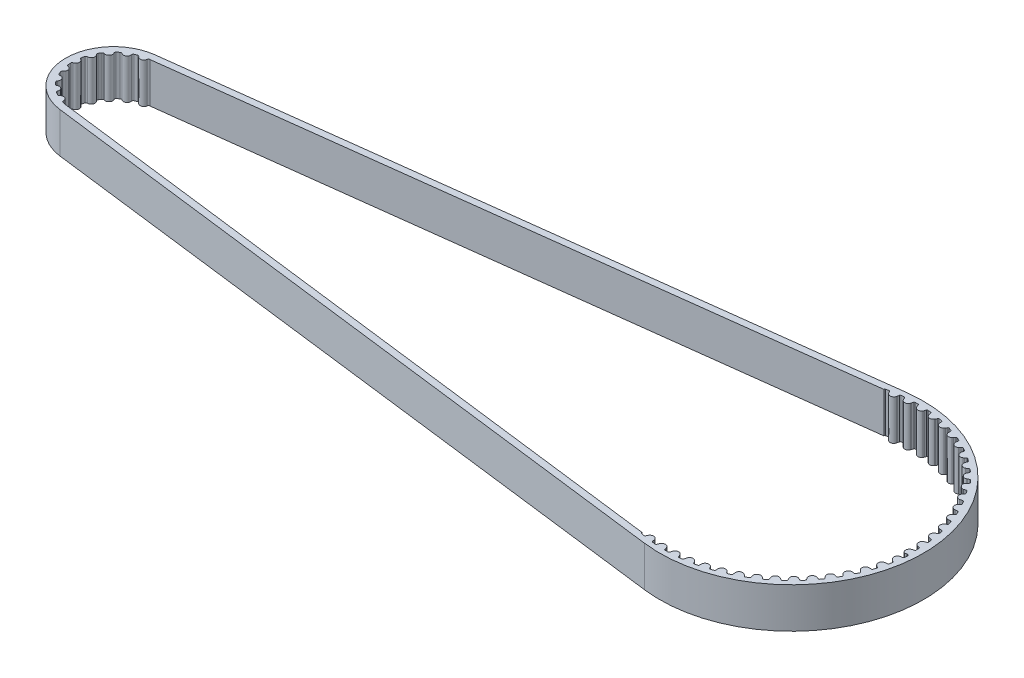
SolidWorks part; units mm, degrees
material "Rubber"
ref_plane "Front Plane" through (0, 0, 0) normal (0, 0, 1) x (1, 0, 0)
ref_plane "Top Plane" through (0, 0, 0) normal (0, 1, 0) x (1, 0, 0)
ref_plane "Right Plane" through (0, 0, 0) normal (1, 0, 0) x (0, 0, -1)
sketch "Sketch1" plane through (0, 0, 0) normal (0, 1, 0) x (1, 0, 0)
  line L0 (0, 0) -> (101, 0)
  line L1 (99.6245, -18.6906) -> (99.7039, -18.4765)
  line L2 (100.8046, -18.5209) -> (100.8665, -18.7407)
  line L3 (101.5857, -18.732) -> (101.6423, -18.5108)
  line L4 (102.7417, -18.4399) -> (102.8262, -18.652)
  line L5 (103.5405, -18.5682) -> (103.5737, -18.3423)
  line L6 (104.6596, -18.1568) -> (104.7659, -18.3589)
  line L7 (105.4675, -18.2009) -> (105.4769, -17.9728)
  line L8 (106.5375, -17.6748) -> (106.6643, -17.8647)
  line L9 (107.3455, -17.6342) -> (107.331, -17.4064)
  line L10 (108.3547, -16.9992) -> (108.5006, -17.1747)
  line L11 (109.1541, -16.8743) -> (109.1158, -16.6492)
  line L12 (110.0913, -16.1373) -> (110.2548, -16.2966)
  line L13 (110.8732, -15.9295) -> (110.8116, -15.7097)
  line L14 (111.7283, -15.0986) -> (111.9075, -15.24)
  line L15 (112.4842, -14.8102) -> (112.4, -14.598)
  line L16 (113.2477, -13.8944) -> (113.4408, -14.0163)
  line L17 (113.9694, -13.5287) -> (113.8635, -13.3264)
  line L18 (114.633, -12.5381) -> (114.8377, -12.6391)
  line L19 (115.3125, -12.0989) -> (115.186, -11.9088)
  line L20 (115.8689, -11.0444) -> (116.0831, -11.1235)
  line L21 (116.4988, -10.5365) -> (116.3531, -10.3608)
  line L22 (116.9419, -9.4296) -> (117.1632, -9.4859)
  line L23 (117.5152, -8.8588) -> (117.352, -8.6992)
  line L24 (117.8402, -7.7116) -> (118.0662, -7.7444)
  line L25 (118.3508, -7.0839) -> (118.1717, -6.9423)
  line L26 (118.5541, -5.9091) -> (118.7822, -5.9181)
  line L27 (118.9962, -5.2315) -> (118.8033, -5.1093)
  line L28 (119.0756, -4.0418) -> (119.3034, -4.0269)
  line L29 (119.4444, -3.3217) -> (119.2398, -3.2204)
  line L30 (119.4169, -2.1154) -> (119.6419, -2.0768)
  line L31 (119.7085, -1.3607) -> (119.4944, -1.2813)
  line L32 (119.3436, -0.3425) -> (119.5634, -0.2806)
  line L33 (119.5547, 0.4386) -> (119.3335, 0.4952)
  line L34 (119.2626, 1.5945) -> (119.4747, 1.6791)
  line L35 (119.3909, 2.3934) -> (119.165, 2.4265)
  line L36 (118.9795, 3.5125) -> (119.1816, 3.6187)
  line L37 (119.0236, 4.3204) -> (118.7955, 4.3297)
  line L38 (118.4975, 5.3903) -> (118.6874, 5.5171)
  line L39 (118.4569, 6.1984) -> (118.2291, 6.1839)
  line L40 (117.8219, 7.2075) -> (117.9975, 7.3535)
  line L41 (117.697, 8.0069) -> (117.472, 7.9687)
  line L42 (116.96, 8.9441) -> (117.1194, 9.1076)
  line L43 (116.7523, 9.7261) -> (116.5324, 9.6645)
  line L44 (115.9213, 10.5811) -> (116.0627, 10.7604)
  line L45 (115.633, 11.3371) -> (115.4208, 11.2529)
  line L46 (114.8944, 12.2477) -> (115.0163, 12.4408)
  line L47 (114.5287, 12.9694) -> (114.3264, 12.8635)
  line L48 (113.5381, 13.633) -> (113.6391, 13.8377)
  line L49 (113.0989, 14.3125) -> (112.9088, 14.186)
  line L50 (112.0444, 14.8689) -> (112.1235, 15.0831)
  line L51 (111.5365, 15.4988) -> (111.3608, 15.3531)
  line L52 (110.4296, 15.9419) -> (110.4859, 16.1632)
  line L53 (109.8588, 16.5152) -> (109.6992, 16.352)
  line L54 (108.7116, 16.8402) -> (108.7444, 17.0662)
  line L55 (108.0839, 17.3508) -> (107.9423, 17.1717)
  line L56 (106.9091, 17.5541) -> (106.9181, 17.7822)
  line L57 (106.2315, 17.9962) -> (106.1093, 17.8033)
  line L58 (105.0418, 18.0756) -> (105.0269, 18.3034)
  line L59 (104.3217, 18.4444) -> (104.2204, 18.2398)
  line L60 (103.1303, 18.399) -> (103.0917, 18.6241)
  line L61 (102.3755, 18.6906) -> (102.2961, 18.4765)
  line L62 (101.1954, 18.5209) -> (101.1335, 18.7407)
  line L63 (100.4143, 18.732) -> (100.3577, 18.5108)
  line L64 (99.2583, 18.4399) -> (99.1738, 18.652)
  line L65 (98.4595, 18.5682) -> (98.4263, 18.3423)
  line L66 (97.3404, 18.1568) -> (97.2341, 18.3589)
  line L67 (96.5325, 18.2009) -> (96.5231, 17.9728)
  line L68 (95.4625, 17.6748) -> (95.3357, 17.8647)
  line L69 (94.6545, 17.6342) -> (94.669, 17.4064)
  line L70 (93.6453, 16.9992) -> (93.4994, 17.1747)
  line L71 (92.8459, 16.8743) -> (92.8842, 16.6492)
  line L72 (91.9087, 16.1373) -> (91.7452, 16.2966)
  line L73 (91.1268, 15.9295) -> (91.1884, 15.7097)
  line L74 (90.2717, 15.0986) -> (90.0925, 15.24)
  line L75 (89.5158, 14.8102) -> (89.6, 14.598)
  line L76 (88.7523, 13.8944) -> (88.5592, 14.0163)
  line L77 (88.0306, 13.5287) -> (88.1365, 13.3264)
  line L78 (87.367, 12.5381) -> (87.1623, 12.6391)
  line L79 (86.6875, 12.0989) -> (86.814, 11.9088)
  line L80 (86.1311, 11.0444) -> (85.9169, 11.1235)
  line L81 (85.5012, 10.5365) -> (85.6469, 10.3608)
  line L82 (85.0581, 9.4296) -> (84.8368, 9.4859)
  line L83 (84.4848, 8.8588) -> (84.648, 8.6992)
  line L84 (84.1598, 7.7116) -> (83.9338, 7.7444)
  line L85 (83.6492, 7.0839) -> (83.8283, 6.9423)
  line L86 (83.4459, 5.9091) -> (83.2178, 5.9181)
  line L87 (83.0038, 5.2315) -> (83.1967, 5.1093)
  line L88 (82.9244, 4.0418) -> (82.6966, 4.0269)
  line L89 (82.5556, 3.3217) -> (82.7602, 3.2204)
  line L90 (82.601, 2.1303) -> (82.3759, 2.0917)
  line L91 (82.3094, 1.3755) -> (82.5235, 1.2961)
  line L92 (82.4791, 0.1954) -> (82.2593, 0.1335)
  line L93 (82.268, -0.5857) -> (82.4892, -0.6423)
  line L94 (82.5601, -1.7417) -> (82.348, -1.8262)
  line L95 (82.4318, -2.5405) -> (82.6577, -2.5737)
  line L96 (82.8432, -3.6596) -> (82.6411, -3.7659)
  line L97 (82.7991, -4.4675) -> (83.0272, -4.4769)
  line L98 (83.3252, -5.5375) -> (83.1353, -5.6643)
  line L99 (83.3658, -6.3455) -> (83.5936, -6.331)
  line L100 (84.0008, -7.3547) -> (83.8253, -7.5006)
  line L101 (84.1257, -8.1541) -> (84.3508, -8.1158)
  line L102 (84.8627, -9.0913) -> (84.7034, -9.2548)
  line L103 (85.0705, -9.8732) -> (85.2903, -9.8116)
  line L104 (85.9014, -10.7283) -> (85.76, -10.9075)
  line L105 (86.1898, -11.4842) -> (86.402, -11.4)
  line L106 (87.1056, -12.2477) -> (86.9837, -12.4408)
  line L107 (87.4713, -12.9694) -> (87.6736, -12.8635)
  line L108 (88.4619, -13.633) -> (88.3609, -13.8377)
  line L109 (88.9011, -14.3125) -> (89.0912, -14.186)
  line L110 (89.9556, -14.8689) -> (89.8765, -15.0831)
  line L111 (90.4635, -15.4988) -> (90.6392, -15.3531)
  line L112 (91.5704, -15.9419) -> (91.5141, -16.1632)
  line L113 (92.1412, -16.5152) -> (92.3008, -16.352)
  line L114 (93.2884, -16.8402) -> (93.2556, -17.0662)
  line L115 (93.9161, -17.3508) -> (94.0577, -17.1717)
  line L116 (95.0909, -17.5541) -> (95.0819, -17.7822)
  line L117 (95.7685, -17.9962) -> (95.8907, -17.8033)
  line L118 (96.9582, -18.0756) -> (96.9731, -18.3034)
  line L119 (97.6783, -18.4444) -> (97.7796, -18.2398)
  line L120 (98.8697, -18.399) -> (98.9083, -18.6241)
  line L121 (-0.8821, -7.0702) -> (98.5701, -19.4775)
  line L122 (-0.8821, 7.0702) -> (98.5701, 19.4775)
  line L123 (98.2274, -18.421) -> (-1.1005, -6.0253)
  line L124 (-0.5636, 6.099) -> (97.864, 18.3626)
  circle A0 centre (0, 0) radius 7.125
  arc A1 (3.5613, -4.8212) -> (2.6742, -5.3656) centre (3.2108, -5.2451) ccw
  arc A2 (2.5625, -5.5912) -> (2.6742, -5.3656) centre (2.4791, -5.4094) ccw
  arc A3 (2.1438, -5.7649) -> (2.5625, -5.5912) centre (0.0074, -0.0246) ccw
  arc A4 (1.9052, -5.6847) -> (2.1438, -5.7649) centre (2.074, -5.5775) ccw
  arc A5 (1.9052, -5.6847) -> (0.8932, -5.9283) centre (1.4408, -5.9795) ccw
  arc A6 (0.7173, -6.1083) -> (0.8932, -5.9283) centre (0.6941, -5.9096) ccw
  arc A7 (0.2653, -6.1441) -> (0.7173, -6.1083) centre (0.0074, -0.0246) ccw
  arc A8 (0.0632, -5.9941) -> (0.2653, -6.1441) centre (0.2569, -5.9443) ccw
  arc A9 (0.0632, -5.9941) -> (-0.9745, -5.9131) centre (-0.4695, -6.131) ccw
  arc A10 (-1.1974, -6.0299) -> (-0.9745, -5.9131) centre (-1.1581, -5.8338) ccw
  arc A11 (-1.6457, -5.8998) -> (-1.1974, -6.0299) centre (0.2848, -0.087) ccw
  arc A12 (-1.7916, -5.6946) -> (-1.6457, -5.8998) centre (-1.592, -5.7071) ccw
  arc A13 (-1.7916, -5.6946) -> (-2.7535, -5.2969) centre (-2.3405, -5.6602) ccw
  arc A14 (-3.0016, -5.3391) -> (-2.7535, -5.2969) centre (-2.9036, -5.1648) ccw
  arc A15 (-3.3883, -5.1024) -> (-3.0016, -5.3391) centre (0, 0) ccw
  arc A16 (-3.4636, -4.8622) -> (-3.3883, -5.1024) centre (-3.2777, -4.9358) ccw
  arc A17 (-3.4636, -4.8622) -> (-4.2555, -4.1868) centre (-3.9751, -4.6599) ccw
  arc A18 (-4.5046, -4.1502) -> (-4.2555, -4.1868) centre (-4.3575, -4.0147) ccw
  arc A19 (-4.7992, -3.8057) -> (-4.5046, -4.1502) centre (0, 0) ccw
  arc A20 (-4.7966, -3.5539) -> (-4.7992, -3.8057) centre (-4.6425, -3.6814) ccw
  arc A21 (-4.7966, -3.5539) -> (-5.341, -2.6668) centre (-5.2205, -3.2034) ccw
  arc A22 (-5.5666, -2.5551) -> (-5.341, -2.6668) centre (-5.3848, -2.4717) ccw
  arc A23 (-5.7403, -2.1364) -> (-5.5666, -2.5551) centre (0, 0) ccw
  arc A24 (-5.6601, -1.8978) -> (-5.7403, -2.1364) centre (-5.5529, -2.0666) ccw
  arc A25 (-5.6601, -1.8978) -> (-5.9037, -0.8858) centre (-5.9549, -1.4334) ccw
  arc A26 (-6.0837, -0.7099) -> (-5.9037, -0.8858) centre (-5.8851, -0.6867) ccw
  arc A27 (-6.1196, -0.2579) -> (-6.0837, -0.7099) centre (0, 0) ccw
  arc A28 (-5.9695, -0.0558) -> (-6.1196, -0.2579) centre (-5.9197, -0.2495) ccw
  arc A29 (-5.9695, -0.0558) -> (-5.8885, 0.9819) centre (-6.1064, 0.4769) ccw
  arc A30 (-6.0053, 1.2048) -> (-5.8885, 0.9819) centre (-5.8092, 1.1655) ccw
  arc A31 (-5.8998, 1.6457) -> (-6.0053, 1.2048) centre (0, 0) ccw
  arc A32 (-5.6946, 1.7916) -> (-5.8998, 1.6457) centre (-5.7071, 1.592) ccw
  arc A33 (-5.6946, 1.7916) -> (-5.2969, 2.7535) centre (-5.6602, 2.3405) ccw
  arc A34 (-5.3391, 3.0016) -> (-5.2969, 2.7535) centre (-5.1648, 2.9036) ccw
  arc A35 (-5.1024, 3.3883) -> (-5.3391, 3.0016) centre (0, 0) ccw
  arc A36 (-4.8622, 3.4636) -> (-5.1024, 3.3883) centre (-4.9358, 3.2777) ccw
  arc A37 (-4.8622, 3.4636) -> (-4.1868, 4.2555) centre (-4.6599, 3.9751) ccw
  arc A38 (-4.1502, 4.5046) -> (-4.1868, 4.2555) centre (-4.0147, 4.3575) ccw
  arc A39 (-3.8057, 4.7992) -> (-4.1502, 4.5046) centre (0, 0) ccw
  arc A40 (-3.5539, 4.7966) -> (-3.8057, 4.7992) centre (-3.6814, 4.6425) ccw
  arc A41 (-3.5539, 4.7966) -> (-2.6668, 5.341) centre (-3.2034, 5.2205) ccw
  arc A42 (-2.5551, 5.5666) -> (-2.6668, 5.341) centre (-2.4717, 5.3848) ccw
  arc A43 (-2.1364, 5.7403) -> (-2.5551, 5.5666) centre (0, 0) ccw
  arc A44 (-1.8978, 5.6601) -> (-2.1364, 5.7403) centre (-2.0666, 5.5529) ccw
  arc A45 (-1.8978, 5.6601) -> (-0.8858, 5.9037) centre (-1.4334, 5.9549) ccw
  arc A46 (-0.7099, 6.0837) -> (-0.8858, 5.9037) centre (-0.6867, 5.8851) ccw
  arc A47 (-0.2579, 6.1196) -> (-0.7099, 6.0837) centre (0, 0) ccw
  arc A48 (-0.0558, 5.9695) -> (-0.2579, 6.1196) centre (-0.2495, 5.9197) ccw
  arc A49 (-0.0558, 5.9695) -> (0.9819, 5.8885) centre (0.4769, 6.1064) ccw
  arc A50 (1.2048, 6.0053) -> (0.9819, 5.8885) centre (1.1655, 5.8092) ccw
  arc A51 (1.6457, 5.8998) -> (1.2048, 6.0053) centre (0, 0) ccw
  arc A52 (1.7916, 5.6946) -> (1.6457, 5.8998) centre (1.592, 5.7071) ccw
  arc A53 (1.7916, 5.6946) -> (2.7535, 5.2969) centre (2.3405, 5.6602) ccw
  arc A54 (3.0016, 5.3391) -> (2.7535, 5.2969) centre (2.9036, 5.1648) ccw
  arc A55 (3.3883, 5.1024) -> (3.0016, 5.3391) centre (0, 0) ccw
  arc A56 (3.4636, 4.8622) -> (3.3883, 5.1024) centre (3.2777, 4.9358) ccw
  arc A57 (3.4636, 4.8622) -> (4.2555, 4.1868) centre (3.9751, 4.6599) ccw
  arc A58 (4.5046, 4.1502) -> (4.2555, 4.1868) centre (4.3575, 4.0147) ccw
  arc A59 (4.7992, 3.8057) -> (4.5046, 4.1502) centre (0, 0) ccw
  arc A60 (4.7966, 3.5539) -> (4.7992, 3.8057) centre (4.6425, 3.6814) ccw
  arc A61 (4.7966, 3.5539) -> (5.341, 2.6668) centre (5.2205, 3.2034) ccw
  arc A62 (5.5666, 2.5551) -> (5.341, 2.6668) centre (5.3848, 2.4717) ccw
  arc A63 (5.7403, 2.1364) -> (5.5666, 2.5551) centre (0, 0) ccw
  arc A64 (5.6601, 1.8978) -> (5.7403, 2.1364) centre (5.5529, 2.0666) ccw
  arc A65 (5.6601, 1.8978) -> (5.9037, 0.8858) centre (5.9549, 1.4334) ccw
  arc A66 (6.0837, 0.7099) -> (5.9037, 0.8858) centre (5.8851, 0.6867) ccw
  arc A67 (6.1196, 0.2579) -> (6.0837, 0.7099) centre (0, 0) ccw
  arc A68 (5.9695, 0.0558) -> (6.1196, 0.2579) centre (5.9197, 0.2495) ccw
  arc A69 (5.9695, 0.0558) -> (5.8959, -1.0064) centre (6.0704, -0.4849) ccw
  arc A70 (6.0127, -1.2294) -> (5.8959, -1.0064) centre (5.8166, -1.1901) ccw
  arc A71 (5.9072, -1.6703) -> (6.0127, -1.2294) centre (0.0074, -0.0246) ccw
  arc A72 (5.702, -1.8162) -> (5.9072, -1.6703) centre (5.7145, -1.6166) ccw
  arc A73 (5.702, -1.8162) -> (5.3043, -2.778) centre (5.6676, -2.3651) ccw
  arc A74 (5.3465, -3.0262) -> (5.3043, -2.778) centre (5.1721, -2.9282) ccw
  arc A75 (5.1098, -3.4129) -> (5.3465, -3.0262) centre (0.0074, -0.0246) ccw
  arc A76 (4.8696, -3.4882) -> (5.1098, -3.4129) centre (4.9432, -3.3022) ccw
  arc A77 (4.8696, -3.4882) -> (4.1941, -4.2801) centre (4.6673, -3.9996) ccw
  arc A78 (4.1576, -4.5292) -> (4.1941, -4.2801) centre (4.0221, -4.3821) ccw
  arc A79 (3.8131, -4.8238) -> (4.1576, -4.5292) centre (0.0074, -0.0246) ccw
  arc A80 (3.5613, -4.8212) -> (3.8131, -4.8238) centre (3.6888, -4.6671) ccw
  arc A81 (98.9083, -18.6241) -> (99.0406, -18.7479) centre (99.0562, -18.5987) ccw
  arc A82 (99.0406, -18.7479) -> (99.4717, -18.7879) centre (101, 0) ccw
  arc A83 (99.4717, -18.7879) -> (99.6245, -18.6906) centre (99.4838, -18.6384) ccw
  arc A84 (99.761, -18.3502) -> (99.7039, -18.4765) centre (100.6414, -18.8243) ccw
  arc A85 (100.7579, -18.3904) -> (99.761, -18.3502) centre (100.2496, -18.6133) ccw
  arc A86 (100.8046, -18.5209) -> (100.7579, -18.3904) centre (99.8421, -18.7921) ccw
  arc A87 (100.8665, -18.7407) -> (101.011, -18.85) centre (101.0109, -18.7) ccw
  arc A88 (101.011, -18.85) -> (101.4439, -18.8448) centre (101, 0) ccw
  arc A89 (101.4439, -18.8448) -> (101.5857, -18.732) centre (101.4404, -18.6948) ccw
  arc A90 (101.6859, -18.3792) -> (101.6423, -18.5108) centre (102.6111, -18.7586) ccw
  arc A91 (102.6815, -18.315) -> (101.6859, -18.3792) centre (102.1994, -18.5898) ccw
  arc A92 (102.7417, -18.4399) -> (102.6815, -18.315) centre (101.8127, -18.8102) ccw
  arc A93 (102.8262, -18.652) -> (102.9813, -18.7456) centre (102.9655, -18.5964) ccw
  arc A94 (102.9813, -18.7456) -> (103.4113, -18.6951) centre (101, 0) ccw
  arc A95 (103.4113, -18.6951) -> (103.5405, -18.5682) centre (103.3921, -18.5464) ccw
  arc A96 (103.6033, -18.2069) -> (103.5737, -18.3423) centre (104.5631, -18.4875) ccw
  arc A97 (104.5868, -18.0389) -> (103.6033, -18.2069) centre (104.136, -18.3626) ccw
  arc A98 (104.6596, -18.1568) -> (104.5868, -18.0389) centre (103.7745, -18.6222) ccw
  arc A99 (104.7659, -18.3589) -> (104.9299, -18.4358) centre (104.8986, -18.2891) ccw
  arc A100 (104.9299, -18.4358) -> (105.3523, -18.3407) centre (101, 0) ccw
  arc A101 (105.3523, -18.3407) -> (105.4675, -18.2009) centre (105.3176, -18.1947) ccw
  arc A102 (105.4921, -17.835) -> (105.4769, -17.9728) centre (106.476, -18.0138) ccw
  arc A103 (106.4527, -17.5651) -> (105.4921, -17.835) centre (106.0382, -17.9342) ccw
  arc A104 (106.5375, -17.6748) -> (106.4527, -17.5651) centre (105.7058, -18.2301) ccw
  arc A105 (106.6643, -17.8647) -> (106.8354, -17.924) centre (106.789, -17.7814) ccw
  arc A106 (106.8354, -17.924) -> (107.2455, -17.7853) centre (101, 0) ccw
  arc A107 (107.2455, -17.7853) -> (107.3455, -17.6342) centre (107.1958, -17.6437) ccw
  arc A108 (107.3318, -17.2677) -> (107.331, -17.4064) centre (108.329, -17.3427) ccw
  arc A109 (108.2589, -16.899) -> (107.3318, -17.2677) centre (107.8852, -17.3093) ccw
  arc A110 (108.3547, -16.9992) -> (108.2589, -16.899) centre (107.5856, -17.6384) ccw
  arc A111 (108.5006, -17.1747) -> (108.677, -17.2159) centre (108.616, -17.0789) ccw
  arc A112 (108.677, -17.2159) -> (109.0704, -17.035) centre (101, 0) ccw
  arc A113 (109.0704, -17.035) -> (109.1541, -16.8743) centre (109.0062, -16.8994) ccw
  arc A114 (109.1021, -16.5113) -> (109.1158, -16.6492) centre (110.1016, -16.4816) ccw
  arc A115 (109.9855, -16.0476) -> (109.1021, -16.5113) centre (109.6568, -16.4948) ccw
  arc A116 (110.0913, -16.1373) -> (109.9855, -16.0476) centre (109.3933, -16.8534) ccw
  arc A117 (110.2548, -16.2966) -> (110.4345, -16.3191) centre (110.3595, -16.1892) ccw
  arc A118 (110.4345, -16.3191) -> (110.8068, -16.0981) centre (101, 0) ccw
  arc A119 (110.8068, -16.0981) -> (110.8732, -15.9295) centre (110.7288, -15.97) ccw
  arc A120 (110.7836, -15.5739) -> (110.8116, -15.7097) centre (111.7746, -15.4399) ccw
  arc A121 (111.6138, -15.0205) -> (110.7836, -15.5739) centre (111.3336, -15.4996) ccw
  arc A122 (111.7283, -15.0986) -> (111.6138, -15.0205) centre (111.1089, -15.8837) ccw
  arc A123 (111.9075, -15.24) -> (112.0887, -15.2435) centre (112.0004, -15.1222) ccw
  arc A124 (112.0887, -15.2435) -> (112.4358, -14.9848) centre (101, 0) ccw
  arc A125 (112.4358, -14.9848) -> (112.4842, -14.8102) centre (112.3448, -14.8656) ccw
  arc A126 (112.3579, -14.466) -> (112.4, -14.598) centre (113.3295, -14.2291) ccw
  arc A127 (113.1257, -13.8287) -> (112.3579, -14.466) centre (112.8971, -14.3345) ccw
  arc A128 (113.2477, -13.8944) -> (113.1257, -13.8287) centre (112.7139, -14.74) ccw
  arc A129 (113.4408, -14.0163) -> (113.6213, -14.0009) centre (113.5209, -13.8895) ccw
  arc A130 (113.6213, -14.0009) -> (113.9395, -13.7074) centre (101, 0) ccw
  arc A131 (113.9395, -13.7074) -> (113.9694, -13.5287) centre (113.8365, -13.5983) ccw
  arc A132 (113.8078, -13.1995) -> (113.8635, -13.3264) centre (114.7493, -12.8624) ccw
  arc A133 (114.5048, -12.4855) -> (113.8078, -13.1995) centre (114.3303, -13.0124) ccw
  arc A134 (114.633, -12.5381) -> (114.5048, -12.4855) centre (114.1904, -13.4348) ccw
  arc A135 (114.8377, -12.6391) -> (115.0156, -12.6049) centre (114.9041, -12.5046) ccw
  arc A136 (115.0156, -12.6049) -> (115.3014, -12.2797) centre (101, 0) ccw
  arc A137 (115.3014, -12.2797) -> (115.3125, -12.0989) centre (115.1876, -12.182) ccw
  arc A138 (115.1174, -11.7884) -> (115.186, -11.9088) centre (116.0184, -11.3547) ccw
  arc A139 (115.7359, -11.0055) -> (115.1174, -11.7884) centre (115.6174, -11.5477) ccw
  arc A140 (115.8689, -11.0444) -> (115.7359, -11.0055) centre (115.5225, -11.9825) ccw
  arc A141 (116.0831, -11.1235) -> (116.2564, -11.0708) centre (116.135, -10.9827) ccw
  arc A142 (116.2564, -11.0708) -> (116.5067, -10.7175) centre (101, 0) ccw
  arc A143 (116.5067, -10.7175) -> (116.4988, -10.5365) centre (116.3833, -10.6323) ccw
  arc A144 (116.2722, -10.2482) -> (116.3531, -10.3608) centre (117.123, -9.7227) ccw
  arc A145 (116.8055, -9.4049) -> (116.2722, -10.2482) centre (116.7444, -9.9565) ccw
  arc A146 (116.9419, -9.4296) -> (116.8055, -9.4049) centre (116.6955, -10.3988) ccw
  arc A147 (117.1632, -9.4859) -> (117.3301, -9.4155) centre (117.2001, -9.3405) ccw
  arc A148 (117.3301, -9.4155) -> (117.542, -9.0379) centre (101, 0) ccw
  arc A149 (117.542, -9.0379) -> (117.5152, -8.8588) centre (117.4104, -8.966) ccw
  arc A150 (117.2598, -8.5956) -> (117.352, -8.6992) centre (118.051, -7.9841) ccw
  arc A151 (117.702, -7.7012) -> (117.2598, -8.5956) centre (117.6989, -8.2562) ccw
  arc A152 (117.8402, -7.7116) -> (117.702, -7.7012) centre (117.6964, -8.7012) ccw
  arc A153 (118.0662, -7.7444) -> (118.2248, -7.6569) centre (118.0877, -7.596) ccw
  arc A154 (118.2248, -7.6569) -> (118.3961, -7.2593) centre (101, 0) ccw
  arc A155 (118.3961, -7.2593) -> (118.3508, -7.0839) centre (118.2577, -7.2016) ccw
  arc A156 (118.0692, -6.8489) -> (118.1717, -6.9423) centre (118.7922, -6.158) ccw
  arc A157 (118.4155, -5.9132) -> (118.0692, -6.8489) centre (118.4705, -6.4655) ccw
  arc A158 (118.5541, -5.9091) -> (118.4155, -5.9132) centre (118.5145, -6.9083) ccw
  arc A159 (118.7822, -5.9181) -> (118.9308, -5.8145) centre (118.7881, -5.7682) ccw
  arc A160 (118.9308, -5.8145) -> (119.0596, -5.4012) centre (101, 0) ccw
  arc A161 (119.0596, -5.4012) -> (118.9962, -5.2315) centre (118.9159, -5.3582) ccw
  arc A162 (118.6916, -5.0272) -> (118.8033, -5.1093) centre (119.3384, -4.2645) ccw
  arc A163 (118.9382, -4.0604) -> (118.6916, -5.0272) centre (119.0506, -4.6039) ccw
  arc A164 (119.0756, -4.0418) -> (118.9382, -4.0604) centre (119.1407, -5.0397) ccw
  arc A165 (119.3034, -4.0269) -> (119.4404, -3.9084) centre (119.2936, -3.8773) ccw
  arc A166 (119.4404, -3.9084) -> (119.5253, -3.4838) centre (101, 0) ccw
  arc A167 (119.5253, -3.4838) -> (119.4444, -3.3217) centre (119.3778, -3.4561) ccw
  arc A168 (119.1381, -3.1356) -> (119.2398, -3.2204) centre (119.8277, -2.4114) ccw
  arc A169 (119.2822, -2.1483) -> (119.1381, -3.1356) centre (119.4508, -2.6771) ccw
  arc A170 (119.4169, -2.1154) -> (119.2822, -2.1483) centre (119.586, -3.101) ccw
  arc A171 (119.6419, -2.0768) -> (119.7658, -1.9446) centre (119.6166, -1.929) ccw
  arc A172 (119.7658, -1.9446) -> (119.8058, -1.5135) centre (101.0179, 0.0148) ccw
  arc A173 (119.8058, -1.5135) -> (119.7085, -1.3607) centre (119.6563, -1.5013) ccw
  arc A174 (119.173, -1.3862) -> (119.4944, -1.2813) centre (119.028, -0.3967) ccw
  arc A175 (119.2132, -0.3892) -> (119.173, -1.3862) centre (119.4361, -0.8975) ccw
  arc A176 (119.3436, -0.3425) -> (119.2132, -0.3892) centre (119.6148, -1.305) ccw
  arc A177 (119.5634, -0.2806) -> (119.6727, -0.1361) centre (119.5227, -0.1362) ccw
  arc A178 (119.6727, -0.1361) -> (119.6675, 0.2968) centre (100.8227, -0.1471) ccw
  arc A179 (119.6675, 0.2968) -> (119.5547, 0.4386) centre (119.5175, 0.2933) ccw
  arc A180 (119.202, 0.5387) -> (119.3335, 0.4952) centre (119.5814, 1.464) ccw
  arc A181 (119.1377, 1.5344) -> (119.202, 0.5387) centre (119.4125, 1.0522) ccw
  arc A182 (119.2626, 1.5945) -> (119.1377, 1.5344) centre (119.6329, 0.6656) ccw
  arc A183 (119.4747, 1.6791) -> (119.5683, 1.8342) centre (119.4191, 1.8184) ccw
  arc A184 (119.5683, 1.8342) -> (119.5179, 2.2642) centre (100.8227, -0.1471) ccw
  arc A185 (119.5179, 2.2642) -> (119.3909, 2.3934) centre (119.3691, 2.245) ccw
  arc A186 (119.0296, 2.4561) -> (119.165, 2.4265) centre (119.3102, 3.4159) ccw
  arc A187 (118.8616, 3.4396) -> (119.0296, 2.4561) centre (119.1853, 2.9888) ccw
  arc A188 (118.9795, 3.5125) -> (118.8616, 3.4396) centre (119.4449, 2.6274) ccw
  arc A189 (119.1816, 3.6187) -> (119.2585, 3.7828) centre (119.1118, 3.7515) ccw
  arc A190 (119.2585, 3.7828) -> (119.1634, 4.2051) centre (100.8227, -0.1471) ccw
  arc A191 (119.1634, 4.2051) -> (119.0236, 4.3204) centre (119.0175, 4.1705) ccw
  arc A192 (118.6577, 4.345) -> (118.7955, 4.3297) centre (118.8365, 5.3289) ccw
  arc A193 (118.3879, 5.3056) -> (118.6577, 4.345) centre (118.7569, 4.8911) ccw
  arc A194 (118.4975, 5.3903) -> (118.3879, 5.3056) centre (119.0529, 4.5587) ccw
  arc A195 (118.6874, 5.5171) -> (118.7467, 5.6883) centre (118.6041, 5.6419) ccw
  arc A196 (118.7467, 5.6883) -> (118.608, 6.0984) centre (100.8227, -0.1471) ccw
  arc A197 (118.608, 6.0984) -> (118.4569, 6.1984) centre (118.4665, 6.0487) ccw
  arc A198 (118.0905, 6.1847) -> (118.2291, 6.1839) centre (118.1654, 7.1818) ccw
  arc A199 (117.7217, 7.1118) -> (118.0905, 6.1847) centre (118.1321, 6.7381) ccw
  arc A200 (117.8219, 7.2075) -> (117.7217, 7.1118) centre (118.4611, 6.4385) ccw
  arc A201 (117.9975, 7.3535) -> (118.0386, 7.5299) centre (117.9016, 7.4688) ccw
  arc A202 (118.0386, 7.5299) -> (117.8577, 7.9233) centre (100.8227, -0.1471) ccw
  arc A203 (117.8577, 7.9233) -> (117.697, 8.0069) centre (117.7222, 7.859) ccw
  arc A204 (117.334, 7.9549) -> (117.472, 7.9687) centre (117.3043, 8.9545) ccw
  arc A205 (116.8704, 8.8384) -> (117.334, 7.9549) centre (117.3175, 8.5097) ccw
  arc A206 (116.96, 8.9441) -> (116.8704, 8.8384) centre (117.6761, 8.2461) ccw
  arc A207 (117.1194, 9.1076) -> (117.1418, 9.2874) centre (117.0119, 9.2123) ccw
  arc A208 (117.1418, 9.2874) -> (116.9208, 9.6597) centre (100.8227, -0.1471) ccw
  arc A209 (116.9208, 9.6597) -> (116.7523, 9.7261) centre (116.7927, 9.5817) ccw
  arc A210 (116.3967, 9.6365) -> (116.5324, 9.6645) centre (116.2627, 10.6274) ccw
  arc A211 (115.8432, 10.4666) -> (116.3967, 9.6365) centre (116.3223, 10.1865) ccw
  arc A212 (115.9213, 10.5811) -> (115.8432, 10.4666) centre (116.7064, 9.9618) ccw
  arc A213 (116.0627, 10.7604) -> (116.0662, 10.9415) centre (115.9449, 10.8533) ccw
  arc A214 (116.0662, 10.9415) -> (115.8075, 11.2887) centre (100.8227, -0.1471) ccw
  arc A215 (115.8075, 11.2887) -> (115.633, 11.3371) centre (115.6883, 11.1977) ccw
  arc A216 (115.2887, 11.2108) -> (115.4208, 11.2529) centre (115.0518, 12.1823) ccw
  arc A217 (114.6515, 11.9786) -> (115.2887, 11.2108) centre (115.3345, 11.8971) ccw
  arc A218 (114.8944, 12.2477) -> (114.6515, 11.9786) centre (115.503, 11.4542) ccw
  arc A219 (115.0163, 12.4408) -> (115.0009, 12.6213) centre (114.8895, 12.5209) ccw
  arc A220 (115.0009, 12.6213) -> (114.7074, 12.9395) centre (101, 0) ccw
  arc A221 (114.7074, 12.9395) -> (114.5287, 12.9694) centre (114.5983, 12.8365) ccw
  arc A222 (114.1995, 12.8078) -> (114.3264, 12.8635) centre (113.8624, 13.7493) ccw
  arc A223 (113.4855, 13.5048) -> (114.1995, 12.8078) centre (114.0124, 13.3303) ccw
  arc A224 (113.5381, 13.633) -> (113.4855, 13.5048) centre (114.4348, 13.1904) ccw
  arc A225 (113.6391, 13.8377) -> (113.6049, 14.0156) centre (113.5046, 13.9041) ccw
  arc A226 (113.6049, 14.0156) -> (113.2797, 14.3014) centre (101, 0) ccw
  arc A227 (113.2797, 14.3014) -> (113.0989, 14.3125) centre (113.182, 14.1876) ccw
  arc A228 (112.7884, 14.1174) -> (112.9088, 14.186) centre (112.3547, 15.0184) ccw
  arc A229 (112.0055, 14.7359) -> (112.7884, 14.1174) centre (112.5477, 14.6174) ccw
  arc A230 (112.0444, 14.8689) -> (112.0055, 14.7359) centre (112.9825, 14.5225) ccw
  arc A231 (112.1235, 15.0831) -> (112.0708, 15.2564) centre (111.9827, 15.135) ccw
  arc A232 (112.0708, 15.2564) -> (111.7175, 15.5067) centre (101, 0) ccw
  arc A233 (111.7175, 15.5067) -> (111.5365, 15.4988) centre (111.6323, 15.3833) ccw
  arc A234 (111.2482, 15.2722) -> (111.3608, 15.3531) centre (110.7227, 16.123) ccw
  arc A235 (110.4049, 15.8055) -> (111.2482, 15.2722) centre (110.9565, 15.7444) ccw
  arc A236 (110.4296, 15.9419) -> (110.4049, 15.8055) centre (111.3988, 15.6955) ccw
  arc A237 (110.4859, 16.1632) -> (110.4155, 16.3301) centre (110.3405, 16.2001) ccw
  arc A238 (110.4155, 16.3301) -> (110.0379, 16.542) centre (101, 0) ccw
  arc A239 (110.0379, 16.542) -> (109.8588, 16.5152) centre (109.966, 16.4104) ccw
  arc A240 (109.5956, 16.2598) -> (109.6992, 16.352) centre (108.9841, 17.051) ccw
  arc A241 (108.7012, 16.702) -> (109.5956, 16.2598) centre (109.2562, 16.6989) ccw
  arc A242 (108.7116, 16.8402) -> (108.7012, 16.702) centre (109.7012, 16.6964) ccw
  arc A243 (108.7444, 17.0662) -> (108.6569, 17.2248) centre (108.596, 17.0877) ccw
  arc A244 (108.6569, 17.2248) -> (108.2593, 17.3961) centre (101, 0) ccw
  arc A245 (108.2593, 17.3961) -> (108.0839, 17.3508) centre (108.2016, 17.2577) ccw
  arc A246 (107.8489, 17.0692) -> (107.9423, 17.1717) centre (107.158, 17.7922) ccw
  arc A247 (106.9132, 17.4155) -> (107.8489, 17.0692) centre (107.4655, 17.4705) ccw
  arc A248 (106.9091, 17.5541) -> (106.9132, 17.4155) centre (107.9083, 17.5145) ccw
  arc A249 (106.9181, 17.7822) -> (106.8145, 17.9308) centre (106.7682, 17.7881) ccw
  arc A250 (106.8145, 17.9308) -> (106.4012, 18.0596) centre (101, 0) ccw
  arc A251 (106.4012, 18.0596) -> (106.2315, 17.9962) centre (106.3582, 17.9159) ccw
  arc A252 (106.0272, 17.6916) -> (106.1093, 17.8033) centre (105.2645, 18.3384) ccw
  arc A253 (105.0604, 17.9382) -> (106.0272, 17.6916) centre (105.6039, 18.0506) ccw
  arc A254 (105.0418, 18.0756) -> (105.0604, 17.9382) centre (106.0397, 18.1407) ccw
  arc A255 (105.0269, 18.3034) -> (104.9084, 18.4404) centre (104.8773, 18.2936) ccw
  arc A256 (104.9084, 18.4404) -> (104.4838, 18.5253) centre (101, 0) ccw
  arc A257 (104.4838, 18.5253) -> (104.3217, 18.4444) centre (104.4561, 18.3778) ccw
  arc A258 (104.1504, 18.1202) -> (104.2204, 18.2398) centre (103.3243, 18.6837) ccw
  arc A259 (103.1631, 18.2644) -> (104.1504, 18.1202) centre (103.6919, 18.4329) ccw
  arc A260 (103.1303, 18.399) -> (103.1631, 18.2644) centre (104.1159, 18.5681) ccw
  arc A261 (103.0917, 18.6241) -> (102.9594, 18.7479) centre (102.9438, 18.5987) ccw
  arc A262 (102.9594, 18.7479) -> (102.5283, 18.7879) centre (101, 0) ccw
  arc A263 (102.5283, 18.7879) -> (102.3755, 18.6906) centre (102.5162, 18.6384) ccw
  arc A264 (102.239, 18.3502) -> (102.2961, 18.4765) centre (101.3586, 18.8243) ccw
  arc A265 (101.2421, 18.3904) -> (102.239, 18.3502) centre (101.7504, 18.6133) ccw
  arc A266 (101.1954, 18.5209) -> (101.2421, 18.3904) centre (102.1579, 18.7921) ccw
  arc A267 (101.1335, 18.7407) -> (100.989, 18.85) centre (100.9891, 18.7) ccw
  arc A268 (100.989, 18.85) -> (100.5561, 18.8448) centre (101, 0) ccw
  arc A269 (100.5561, 18.8448) -> (100.4143, 18.732) centre (100.5596, 18.6948) ccw
  arc A270 (100.3141, 18.3792) -> (100.3577, 18.5108) centre (99.3889, 18.7586) ccw
  arc A271 (99.3185, 18.315) -> (100.3141, 18.3792) centre (99.8006, 18.5898) ccw
  arc A272 (99.2583, 18.4399) -> (99.3185, 18.315) centre (100.1873, 18.8102) ccw
  arc A273 (99.1738, 18.652) -> (99.0187, 18.7456) centre (99.0345, 18.5964) ccw
  arc A274 (99.0187, 18.7456) -> (98.5887, 18.6951) centre (101, 0) ccw
  arc A275 (98.5887, 18.6951) -> (98.4595, 18.5682) centre (98.6079, 18.5464) ccw
  arc A276 (98.3967, 18.2069) -> (98.4263, 18.3423) centre (97.4369, 18.4875) ccw
  arc A277 (97.4132, 18.0389) -> (98.3967, 18.2069) centre (97.864, 18.3626) ccw
  arc A278 (97.3404, 18.1568) -> (97.4132, 18.0389) centre (98.2255, 18.6222) ccw
  arc A279 (97.2341, 18.3589) -> (97.0701, 18.4358) centre (97.1014, 18.2891) ccw
  arc A280 (97.0701, 18.4358) -> (96.6477, 18.3407) centre (101, 0) ccw
  arc A281 (96.6477, 18.3407) -> (96.5325, 18.2009) centre (96.6824, 18.1947) ccw
  arc A282 (96.5079, 17.835) -> (96.5231, 17.9728) centre (95.524, 18.0138) ccw
  arc A283 (95.5473, 17.5651) -> (96.5079, 17.835) centre (95.9618, 17.9342) ccw
  arc A284 (95.4625, 17.6748) -> (95.5473, 17.5651) centre (96.2942, 18.2301) ccw
  arc A285 (95.3357, 17.8647) -> (95.1646, 17.924) centre (95.211, 17.7814) ccw
  arc A286 (95.1646, 17.924) -> (94.7545, 17.7853) centre (101, 0) ccw
  arc A287 (94.7545, 17.7853) -> (94.6545, 17.6342) centre (94.8042, 17.6437) ccw
  arc A288 (94.6682, 17.2677) -> (94.669, 17.4064) centre (93.671, 17.3427) ccw
  arc A289 (93.7411, 16.899) -> (94.6682, 17.2677) centre (94.1148, 17.3093) ccw
  arc A290 (93.6453, 16.9992) -> (93.7411, 16.899) centre (94.4144, 17.6384) ccw
  arc A291 (93.4994, 17.1747) -> (93.323, 17.2159) centre (93.384, 17.0789) ccw
  arc A292 (93.323, 17.2159) -> (92.9296, 17.035) centre (101, 0) ccw
  arc A293 (92.9296, 17.035) -> (92.8459, 16.8743) centre (92.9938, 16.8994) ccw
  arc A294 (92.8979, 16.5113) -> (92.8842, 16.6492) centre (91.8984, 16.4816) ccw
  arc A295 (92.0145, 16.0476) -> (92.8979, 16.5113) centre (92.3432, 16.4948) ccw
  arc A296 (91.9087, 16.1373) -> (92.0145, 16.0476) centre (92.6067, 16.8534) ccw
  arc A297 (91.7452, 16.2966) -> (91.5655, 16.3191) centre (91.6405, 16.1892) ccw
  arc A298 (91.5655, 16.3191) -> (91.1932, 16.0981) centre (101, 0) ccw
  arc A299 (91.1932, 16.0981) -> (91.1268, 15.9295) centre (91.2712, 15.97) ccw
  arc A300 (91.2164, 15.5739) -> (91.1884, 15.7097) centre (90.2254, 15.4399) ccw
  arc A301 (90.3862, 15.0205) -> (91.2164, 15.5739) centre (90.6664, 15.4996) ccw
  arc A302 (90.2717, 15.0986) -> (90.3862, 15.0205) centre (90.8911, 15.8837) ccw
  arc A303 (90.0925, 15.24) -> (89.9113, 15.2435) centre (89.9996, 15.1222) ccw
  arc A304 (89.9113, 15.2435) -> (89.5642, 14.9848) centre (101, 0) ccw
  arc A305 (89.5642, 14.9848) -> (89.5158, 14.8102) centre (89.6552, 14.8656) ccw
  arc A306 (89.6421, 14.466) -> (89.6, 14.598) centre (88.6705, 14.2291) ccw
  arc A307 (88.8743, 13.8287) -> (89.6421, 14.466) centre (89.1029, 14.3345) ccw
  arc A308 (88.7523, 13.8944) -> (88.8743, 13.8287) centre (89.2861, 14.74) ccw
  arc A309 (88.5592, 14.0163) -> (88.3787, 14.0009) centre (88.4791, 13.8895) ccw
  arc A310 (88.3787, 14.0009) -> (88.0605, 13.7074) centre (101, 0) ccw
  arc A311 (88.0605, 13.7074) -> (88.0306, 13.5287) centre (88.1635, 13.5983) ccw
  arc A312 (88.1922, 13.1995) -> (88.1365, 13.3264) centre (87.2507, 12.8624) ccw
  arc A313 (87.4952, 12.4855) -> (88.1922, 13.1995) centre (87.6697, 13.0124) ccw
  arc A314 (87.367, 12.5381) -> (87.4952, 12.4855) centre (87.8096, 13.4348) ccw
  arc A315 (87.1623, 12.6391) -> (86.9844, 12.6049) centre (87.0959, 12.5046) ccw
  arc A316 (86.9844, 12.6049) -> (86.6986, 12.2797) centre (101, 0) ccw
  arc A317 (86.6986, 12.2797) -> (86.6875, 12.0989) centre (86.8124, 12.182) ccw
  arc A318 (86.8826, 11.7884) -> (86.814, 11.9088) centre (85.9816, 11.3547) ccw
  arc A319 (86.2641, 11.0055) -> (86.8826, 11.7884) centre (86.3826, 11.5477) ccw
  arc A320 (86.1311, 11.0444) -> (86.2641, 11.0055) centre (86.4775, 11.9825) ccw
  arc A321 (85.9169, 11.1235) -> (85.7436, 11.0708) centre (85.865, 10.9827) ccw
  arc A322 (85.7436, 11.0708) -> (85.4933, 10.7175) centre (101, 0) ccw
  arc A323 (85.4933, 10.7175) -> (85.5012, 10.5365) centre (85.6167, 10.6323) ccw
  arc A324 (85.7278, 10.2482) -> (85.6469, 10.3608) centre (84.877, 9.7227) ccw
  arc A325 (85.1945, 9.4049) -> (85.7278, 10.2482) centre (85.2556, 9.9565) ccw
  arc A326 (85.0581, 9.4296) -> (85.1945, 9.4049) centre (85.3045, 10.3988) ccw
  arc A327 (84.8368, 9.4859) -> (84.6699, 9.4155) centre (84.7999, 9.3405) ccw
  arc A328 (84.6699, 9.4155) -> (84.458, 9.0379) centre (101, 0) ccw
  arc A329 (84.458, 9.0379) -> (84.4848, 8.8588) centre (84.5896, 8.966) ccw
  arc A330 (84.7402, 8.5956) -> (84.648, 8.6992) centre (83.949, 7.9841) ccw
  arc A331 (84.298, 7.7012) -> (84.7402, 8.5956) centre (84.3011, 8.2562) ccw
  arc A332 (84.1598, 7.7116) -> (84.298, 7.7012) centre (84.3036, 8.7012) ccw
  arc A333 (83.9338, 7.7444) -> (83.7752, 7.6569) centre (83.9123, 7.596) ccw
  arc A334 (83.7752, 7.6569) -> (83.6039, 7.2593) centre (101, 0) ccw
  arc A335 (83.6039, 7.2593) -> (83.6492, 7.0839) centre (83.7423, 7.2016) ccw
  arc A336 (83.9308, 6.8489) -> (83.8283, 6.9423) centre (83.2078, 6.158) ccw
  arc A337 (83.5845, 5.9132) -> (83.9308, 6.8489) centre (83.5295, 6.4655) ccw
  arc A338 (83.4459, 5.9091) -> (83.5845, 5.9132) centre (83.4855, 6.9083) ccw
  arc A339 (83.2178, 5.9181) -> (83.0692, 5.8145) centre (83.2119, 5.7682) ccw
  arc A340 (83.0692, 5.8145) -> (82.9404, 5.4012) centre (101, 0) ccw
  arc A341 (82.9404, 5.4012) -> (83.0038, 5.2315) centre (83.0841, 5.3582) ccw
  arc A342 (83.3084, 5.0272) -> (83.1967, 5.1093) centre (82.6616, 4.2645) ccw
  arc A343 (83.0618, 4.0604) -> (83.3084, 5.0272) centre (82.9494, 4.6039) ccw
  arc A344 (82.9244, 4.0418) -> (83.0618, 4.0604) centre (82.8593, 5.0397) ccw
  arc A345 (82.6966, 4.0269) -> (82.5596, 3.9084) centre (82.7064, 3.8773) ccw
  arc A346 (82.5596, 3.9084) -> (82.4747, 3.4838) centre (101, 0) ccw
  arc A347 (82.4747, 3.4838) -> (82.5556, 3.3217) centre (82.6222, 3.4561) ccw
  arc A348 (82.8798, 3.1504) -> (82.7602, 3.2204) centre (82.3163, 2.3243) ccw
  arc A349 (82.7356, 2.1631) -> (82.8798, 3.1504) centre (82.5671, 2.6919) ccw
  arc A350 (82.601, 2.1303) -> (82.7356, 2.1631) centre (82.4319, 3.1159) ccw
  arc A351 (82.3759, 2.0917) -> (82.2521, 1.9594) centre (82.4013, 1.9438) ccw
  arc A352 (82.2521, 1.9594) -> (82.2121, 1.5283) centre (101, 0) ccw
  arc A353 (82.2121, 1.5283) -> (82.3094, 1.3755) centre (82.3616, 1.5162) ccw
  arc A354 (82.6498, 1.239) -> (82.5235, 1.2961) centre (82.1757, 0.3586) ccw
  arc A355 (82.6096, 0.2421) -> (82.6498, 1.239) centre (82.3867, 0.7504) ccw
  arc A356 (82.4791, 0.1954) -> (82.6096, 0.2421) centre (82.2079, 1.1579) ccw
  arc A357 (82.2593, 0.1335) -> (82.15, -0.011) centre (82.3, -0.0109) ccw
  arc A358 (82.15, -0.011) -> (82.1552, -0.4439) centre (101, 0) ccw
  arc A359 (82.1552, -0.4439) -> (82.268, -0.5857) centre (82.3052, -0.4404) ccw
  arc A360 (82.6208, -0.6859) -> (82.4892, -0.6423) centre (82.2414, -1.6111) ccw
  arc A361 (82.685, -1.6815) -> (82.6208, -0.6859) centre (82.4102, -1.1994) ccw
  arc A362 (82.5601, -1.7417) -> (82.685, -1.6815) centre (82.1898, -0.8127) ccw
  arc A363 (82.348, -1.8262) -> (82.2544, -1.9813) centre (82.4036, -1.9655) ccw
  arc A364 (82.2544, -1.9813) -> (82.3049, -2.4113) centre (101, 0) ccw
  arc A365 (82.3049, -2.4113) -> (82.4318, -2.5405) centre (82.4536, -2.3921) ccw
  arc A366 (82.7931, -2.6033) -> (82.6577, -2.5737) centre (82.5125, -3.5631) ccw
  arc A367 (82.9611, -3.5868) -> (82.7931, -2.6033) centre (82.6374, -3.136) ccw
  arc A368 (82.8432, -3.6596) -> (82.9611, -3.5868) centre (82.3778, -2.7745) ccw
  arc A369 (82.6411, -3.7659) -> (82.5642, -3.9299) centre (82.7109, -3.8986) ccw
  arc A370 (82.5642, -3.9299) -> (82.6593, -4.3523) centre (101, 0) ccw
  arc A371 (82.6593, -4.3523) -> (82.7991, -4.4675) centre (82.8053, -4.3176) ccw
  arc A372 (83.165, -4.4921) -> (83.0272, -4.4769) centre (82.9862, -5.476) ccw
  arc A373 (83.4349, -5.4527) -> (83.165, -4.4921) centre (83.0658, -5.0382) ccw
  arc A374 (83.3252, -5.5375) -> (83.4349, -5.4527) centre (82.7699, -4.7058) ccw
  arc A375 (83.1353, -5.6643) -> (83.076, -5.8354) centre (83.2186, -5.789) ccw
  arc A376 (83.076, -5.8354) -> (83.2147, -6.2455) centre (101, 0) ccw
  arc A377 (83.2147, -6.2455) -> (83.3658, -6.3455) centre (83.3563, -6.1958) ccw
  arc A378 (83.7323, -6.3318) -> (83.5936, -6.331) centre (83.6573, -7.329) ccw
  arc A379 (84.101, -7.2589) -> (83.7323, -6.3318) centre (83.6907, -6.8852) ccw
  arc A380 (84.0008, -7.3547) -> (84.101, -7.2589) centre (83.3616, -6.5856) ccw
  arc A381 (83.8253, -7.5006) -> (83.7841, -7.677) centre (83.9211, -7.616) ccw
  arc A382 (83.7841, -7.677) -> (83.965, -8.0704) centre (101, 0) ccw
  arc A383 (83.965, -8.0704) -> (84.1257, -8.1541) centre (84.1006, -8.0062) ccw
  arc A384 (84.4887, -8.1021) -> (84.3508, -8.1158) centre (84.5184, -9.1016) ccw
  arc A385 (84.9524, -8.9855) -> (84.4887, -8.1021) centre (84.5052, -8.6568) ccw
  arc A386 (84.8627, -9.0913) -> (84.9524, -8.9855) centre (84.1466, -8.3933) ccw
  arc A387 (84.7034, -9.2548) -> (84.6809, -9.4345) centre (84.8108, -9.3595) ccw
  arc A388 (84.6809, -9.4345) -> (84.9019, -9.8068) centre (101, 0) ccw
  arc A389 (84.9019, -9.8068) -> (85.0705, -9.8732) centre (85.03, -9.7288) ccw
  arc A390 (85.4261, -9.7836) -> (85.2903, -9.8116) centre (85.5601, -10.7746) ccw
  arc A391 (85.9795, -10.6138) -> (85.4261, -9.7836) centre (85.5004, -10.3336) ccw
  arc A392 (85.9014, -10.7283) -> (85.9795, -10.6138) centre (85.1163, -10.1089) ccw
  arc A393 (85.76, -10.9075) -> (85.7565, -11.0887) centre (85.8778, -11.0004) ccw
  arc A394 (85.7565, -11.0887) -> (86.0152, -11.4358) centre (101, 0) ccw
  arc A395 (86.0152, -11.4358) -> (86.1898, -11.4842) centre (86.1344, -11.3448) ccw
  arc A396 (86.534, -11.3579) -> (86.402, -11.4) centre (86.7709, -12.3295) ccw
  arc A397 (87.1713, -12.1257) -> (86.534, -11.3579) centre (86.6655, -11.8971) ccw
  arc A398 (87.1056, -12.2477) -> (87.1713, -12.1257) centre (86.26, -11.7139) ccw
  arc A399 (86.9837, -12.4408) -> (86.9991, -12.6213) centre (87.1105, -12.5209) ccw
  arc A400 (86.9991, -12.6213) -> (87.2926, -12.9395) centre (101, 0) ccw
  arc A401 (87.2926, -12.9395) -> (87.4713, -12.9694) centre (87.4017, -12.8365) ccw
  arc A402 (87.8005, -12.8078) -> (87.6736, -12.8635) centre (88.1376, -13.7493) ccw
  arc A403 (88.5145, -13.5048) -> (87.8005, -12.8078) centre (87.9876, -13.3303) ccw
  arc A404 (88.4619, -13.633) -> (88.5145, -13.5048) centre (87.5652, -13.1904) ccw
  arc A405 (88.3609, -13.8377) -> (88.3951, -14.0156) centre (88.4954, -13.9041) ccw
  arc A406 (88.3951, -14.0156) -> (88.7203, -14.3014) centre (101, 0) ccw
  arc A407 (88.7203, -14.3014) -> (88.9011, -14.3125) centre (88.818, -14.1876) ccw
  arc A408 (89.2116, -14.1174) -> (89.0912, -14.186) centre (89.6453, -15.0184) ccw
  arc A409 (89.9945, -14.7359) -> (89.2116, -14.1174) centre (89.4523, -14.6174) ccw
  arc A410 (89.9556, -14.8689) -> (89.9945, -14.7359) centre (89.0175, -14.5225) ccw
  arc A411 (89.8765, -15.0831) -> (89.9292, -15.2564) centre (90.0173, -15.135) ccw
  arc A412 (89.9292, -15.2564) -> (90.2825, -15.5067) centre (101, 0) ccw
  arc A413 (90.2825, -15.5067) -> (90.4635, -15.4988) centre (90.3677, -15.3833) ccw
  arc A414 (90.7518, -15.2722) -> (90.6392, -15.3531) centre (91.2773, -16.123) ccw
  arc A415 (91.5951, -15.8055) -> (90.7518, -15.2722) centre (91.0435, -15.7444) ccw
  arc A416 (91.5704, -15.9419) -> (91.5951, -15.8055) centre (90.6012, -15.6955) ccw
  arc A417 (91.5141, -16.1632) -> (91.5845, -16.3301) centre (91.6595, -16.2001) ccw
  arc A418 (91.5845, -16.3301) -> (91.9621, -16.542) centre (101, 0) ccw
  arc A419 (91.9621, -16.542) -> (92.1412, -16.5152) centre (92.034, -16.4104) ccw
  arc A420 (92.4044, -16.2598) -> (92.3008, -16.352) centre (93.0159, -17.051) ccw
  arc A421 (93.2988, -16.702) -> (92.4044, -16.2598) centre (92.7438, -16.6989) ccw
  arc A422 (93.2884, -16.8402) -> (93.2988, -16.702) centre (92.2988, -16.6964) ccw
  arc A423 (93.2556, -17.0662) -> (93.3431, -17.2248) centre (93.404, -17.0877) ccw
  arc A424 (93.3431, -17.2248) -> (93.7407, -17.3961) centre (101, 0) ccw
  arc A425 (93.7407, -17.3961) -> (93.9161, -17.3508) centre (93.7984, -17.2577) ccw
  arc A426 (94.1511, -17.0692) -> (94.0577, -17.1717) centre (94.842, -17.7922) ccw
  arc A427 (95.0868, -17.4155) -> (94.1511, -17.0692) centre (94.5345, -17.4705) ccw
  arc A428 (95.0909, -17.5541) -> (95.0868, -17.4155) centre (94.0917, -17.5145) ccw
  arc A429 (95.0819, -17.7822) -> (95.1855, -17.9308) centre (95.2318, -17.7881) ccw
  arc A430 (95.1855, -17.9308) -> (95.5988, -18.0596) centre (101, 0) ccw
  arc A431 (95.5988, -18.0596) -> (95.7685, -17.9962) centre (95.6418, -17.9159) ccw
  arc A432 (95.9728, -17.6916) -> (95.8907, -17.8033) centre (96.7355, -18.3384) ccw
  arc A433 (96.9396, -17.9382) -> (95.9728, -17.6916) centre (96.3961, -18.0506) ccw
  arc A434 (96.9582, -18.0756) -> (96.9396, -17.9382) centre (95.9603, -18.1407) ccw
  arc A435 (96.9731, -18.3034) -> (97.0916, -18.4404) centre (97.1227, -18.2936) ccw
  arc A436 (97.0916, -18.4404) -> (97.5162, -18.5253) centre (101, 0) ccw
  arc A437 (97.5162, -18.5253) -> (97.6783, -18.4444) centre (97.5439, -18.3778) ccw
  arc A438 (97.8496, -18.1202) -> (97.7796, -18.2398) centre (98.6757, -18.6837) ccw
  arc A439 (98.8369, -18.2644) -> (97.8496, -18.1202) centre (98.3081, -18.4329) ccw
  arc A440 (98.8697, -18.399) -> (98.8369, -18.2644) centre (97.8841, -18.5681) ccw
  circle A441 centre (0, 0) radius 6.125 construction
  circle A442 centre (101, 0) radius 18.6285 construction
  circle A443 centre (101, 0) radius 19.6285
  point P1012 (-0.5636, 6.099)
  point P1013 (-0.2495, -6.1064)
  point P1014 (98.2255, -18.4329)
  point P1015 (97.8841, 18.3626)
  point P1016 (-1.1079, -6.0008)
  point P1017 (0, 0)
  point P1018 (0, 0)
  point P1019 (0, 0)
  point P1020 (0, 0)
  point P1021 (0, 0)
  point P1022 (0, 0)
  point P1023 (98.4429, 18.4552)
  dimension "D2" = 1
  dimension "D3" = 12.25
  dimension "D4" = 1
  dimension "D1" = 101
extrude "Boss-Extrude1" add sketch "Sketch1" along normal blind 6 contours A443 L124 L67 A281 A280 A279 L66 A278 A277 A276 L65 A275 A274 A273 L64 A272 A271 A270 L63 A269 A268 A267 L62 A266 A265 A264 L61 A263 A262 A261 L60 A260 A259 A258 L59 A257 A256 A255 L58 A254 A253 A252 L57 A251 A250 A249 L56 | A443 L123 A0 L121 | A443 L122 A0 L124 | A47 L124 A0 L123 A10 A11 A12 A13 A14 A15 A16 A17 A18 A19 A20 A21 A22 A23 A24 A25 A26 A27 A28 A29 A30 A31 A32 A33 A34 A35 A36 A37 A38 A39 A40 A41 A42 A43 A44 A45 A46 region at (48.1764, 0, -12.6883) region at (1.1269, 0, -6.485) region at (48.0502, 0, 12.674) region at (95.6014, 0, -18.3686)
